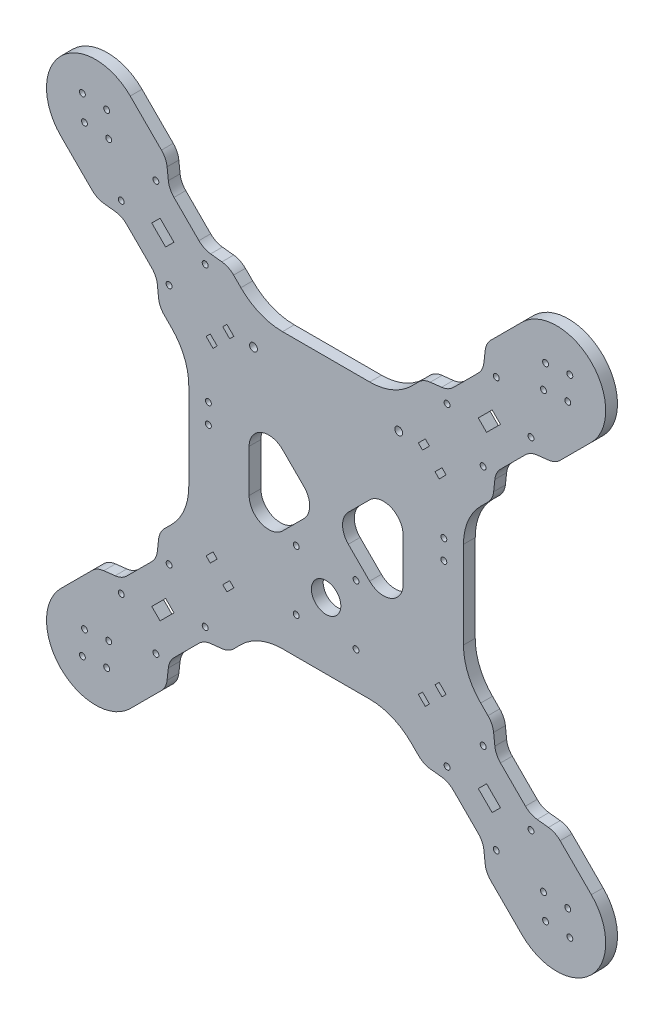
SolidWorks part; units mm, degrees
ref_plane "Front Plane" through (0, 0, 0) normal (0, 0, 1) x (1, 0, 0)
ref_plane "Top Plane" through (0, 0, 0) normal (0, 1, 0) x (1, 0, 0)
ref_plane "Right Plane" through (0, 0, 0) normal (1, 0, 0) x (0, 0, -1)
sketch "Sketch4" plane through (0, 0, 0) normal (0, 0, 1) x (1, 0, 0)
  line L0 (-117.5, 117.5) -> (117.5, -117.5) construction
  line L1 (-117.5, -117.5) -> (117.5, 117.5) construction
  line L2 (-1000, 0) -> (49000, 0) construction
  line L3 (0, -1000) -> (0, 49000) construction
  line L4 (-70, -34.6447) -> (-70, 34.6447)
  line L5 (34.6447, 70) -> (-34.6447, 70)
  line L6 (-70, 34.6447) -> (-135.1777, 99.8223)
  line L7 (-34.6447, 70) -> (-99.8223, 135.1777)
  line L8 (-135.1777, 99.8223) -> (-99.8223, 135.1777) construction
  line L9 (70, -34.6447) -> (70, 34.6447)
  line L10 (70, 34.6447) -> (135.1777, 99.8223)
  line L11 (34.6447, 70) -> (99.8223, 135.1777)
  line L12 (70, -34.6447) -> (135.1777, -99.8223)
  line L13 (34.6447, -70) -> (99.8223, -135.1777)
  line L14 (34.6447, -70) -> (-34.6447, -70)
  line L15 (-34.6447, -70) -> (-99.8223, -135.1777)
  line L16 (-70, -34.6447) -> (-135.1777, -99.8223)
  line L17 (-124.5711, 89.2157) -> (-89.2157, 124.5711) construction
  line L18 (-120.3284, 84.9731) -> (-84.9731, 120.3284) construction
  arc A0 (-135.1777, 99.8223) -> (-99.8223, 135.1777) centre (-117.5, 117.5) cw
  arc A1 (135.1777, 99.8223) -> (99.8223, 135.1777) centre (117.5, 117.5) ccw
  arc A2 (135.1777, -99.8223) -> (99.8223, -135.1777) centre (117.5, -117.5) cw
  arc A3 (-135.1777, -99.8223) -> (-99.8223, -135.1777) centre (-117.5, -117.5) ccw
  point P13 (-117.5, 117.5)
  point P17 (-135.1777, 135.1777)
  point P19 (0, 70)
  point P24 (70, 0)
  point P31 (-70, 0)
  dimension "D6" = 40
  dimension "D1" = 235
  dimension "D2" = 235
  dimension "D3" = 70
  dimension "D4" = 70
  dimension "D5" = 50
  dimension "D7" = 6
extrude "Boss-Extrude1" add sketch "Sketch4" along normal blind 6
fillet "Fillet1" radius 30 8 edges at (34.6447, -70, 3) (70, -34.6447, 3) (70, 34.6447, 3) (34.6447, 70, 3) (-34.6447, 70, 3) (-70, 34.6447, 3) (-70, -34.6447, 3) (-34.6447, -70, 3)
sketch "Sketch8" plane through (0, 0, 6) normal (0, 0, 1) x (1, 0, 0)
  line L0 (-120.3284, 84.9731) -> (-84.9731, 120.3284) construction
  line L1 (-117.5, 117.5) -> (117.5, -117.5) construction
  line L2 (-88.8622, 84.6195) -> (-84.6195, 88.8622)
  line L3 (-88.8622, 84.6195) -> (-81.7911, 77.5485)
  line L4 (-84.6195, 88.8622) -> (-77.5485, 81.7911)
  line L5 (-81.7911, 77.5485) -> (-77.5485, 81.7911)
  circle A0 centre (-104.4185, 86.7409) radius 1.5
  circle A2 centre (-80.0233, 61.6386) radius 1.5
  circle A4 centre (-86.7409, 104.4185) radius 1.5
  circle A5 centre (-61.6386, 80.0233) radius 1.5
  dimension "D1" = 3
  dimension "D2" = 10
  dimension "D3" = 12.5
  dimension "D4" = 13
  dimension "D5" = 45
  dimension "D6" = 10
  dimension "D7" = 12.5
  dimension "D8" = 45
  dimension "D9" = 13
  dimension "D10" = 6
  dimension "D11" = 3
  dimension "D12" = 22.5
  dimension "D13" = 10
sketch "Sketch9" plane through (0, 0, 6) normal (0, 0, 1) x (1, 0, 0)
  line L0 (-135.1777, 99.8223) -> (-99.8223, 135.1777) construction
  line L1 (-117.5, 117.5) -> (117.5, -117.5) construction
  circle A0 centre (-124.2175, 124.2175) radius 1.5
  circle A1 centre (-110.7825, 110.7825) radius 1.5
  circle A2 centre (-123.1569, 111.8431) radius 1.5
  circle A3 centre (-111.8431, 123.1569) radius 1.5
  dimension "D5" = 3
  dimension "D1" = 8
  dimension "D2" = 8
  dimension "D3" = 9.5
  dimension "D4" = 9.5
extrude "Cut-Extrude1" cut sketch "Sketch8" against normal through all both and the other way through all
extrude "Cut-Extrude2" cut sketch "Sketch9" against normal through all both and the other way through all
mirror "Mirror1" about plane through (0, 0, 0) normal (1, 0, 0) of "Cut-Extrude2", "Cut-Extrude1"
mirror "Mirror2" about plane through (0, 0, 0) normal (0, 1, 0) of "Mirror1"
sketch "Sketch10" plane through (0, 0, 6) normal (0, 0, 1) x (1, 0, 0)
  line L0 (-70, -34.6447) -> (-70, 34.6447) construction
  line L1 (70, -34.6447) -> (70, 34.6447) construction
  line L2 (34.6447, 70) -> (-34.6447, 70) construction
  line L3 (-49.1421, -53.3848) -> (-47.0208, -55.5061)
  line L4 (0, -201000) -> (0, 249000) construction
  line L5 (-201000, 0) -> (249000, 0) construction
  line L6 (-4.2426, 0) -> (-39.2426, 35)
  line L7 (-39.2426, 35) -> (-39.2426, -35)
  line L8 (-39.2426, -35) -> (-4.2426, 0)
  line L9 (-117.5, 117.5) -> (117.5, -117.5) construction
  line L10 (-117.5, -117.5) -> (117.5, 117.5) construction
  line L11 (0, -3.3) -> (0, 3.3) construction
  line L12 (39.2426, 35) -> (39.2426, -35)
  line L13 (4.2426, 0) -> (39.2426, 35)
  line L14 (39.2426, -35) -> (4.2426, 0)
  line L21 (3.3, 0) -> (-3.3, 0) construction
  line L22 (-57.6274, -44.8995) -> (-55.5061, -47.0208)
  line L23 (-59.0416, -50.5563) -> (-55.5061, -47.0208)
  line L24 (-61.163, -48.435) -> (-59.0416, -50.5563)
  line L25 (-61.163, 48.435) -> (-59.0416, 50.5563)
  line L26 (-61.163, 48.435) -> (-57.6274, 44.8995)
  line L27 (-57.6274, 44.8995) -> (-55.5061, 47.0208)
  line L28 (-59.0416, 50.5563) -> (-55.5061, 47.0208)
  line L29 (-61.163, -48.435) -> (-57.6274, -44.8995)
  line L30 (57.6274, 44.8995) -> (55.5061, 47.0208)
  line L31 (59.0416, 50.5563) -> (55.5061, 47.0208)
  line L32 (61.163, 48.435) -> (59.0416, 50.5563)
  line L33 (61.163, 48.435) -> (57.6274, 44.8995)
  line L34 (61.163, -48.435) -> (57.6274, -44.8995)
  line L35 (61.163, -48.435) -> (59.0416, -50.5563)
  line L36 (59.0416, -50.5563) -> (55.5061, -47.0208)
  line L37 (57.6274, -44.8995) -> (55.5061, -47.0208)
  line L38 (-52.6777, 56.9203) -> (-50.5563, 59.0416)
  line L39 (-52.6777, 56.9203) -> (-49.1421, 53.3848)
  line L40 (-49.1421, 53.3848) -> (-47.0208, 55.5061)
  line L41 (-50.5563, 59.0416) -> (-47.0208, 55.5061)
  line L42 (-50.5563, -59.0416) -> (-47.0208, -55.5061)
  line L43 (-52.6777, -56.9203) -> (-50.5563, -59.0416)
  line L44 (-52.6777, -56.9203) -> (-49.1421, -53.3848)
  line L45 (52.6777, -56.9203) -> (49.1421, -53.3848)
  line L46 (52.6777, -56.9203) -> (50.5563, -59.0416)
  line L47 (50.5563, -59.0416) -> (47.0208, -55.5061)
  line L48 (49.1421, -53.3848) -> (47.0208, -55.5061)
  line L49 (49.1421, 53.3848) -> (47.0208, 55.5061)
  line L50 (50.5563, 59.0416) -> (47.0208, 55.5061)
  line L51 (52.6777, 56.9203) -> (50.5563, 59.0416)
  line L52 (52.6777, 56.9203) -> (49.1421, 53.3848)
  line L53 (-15.25, -21) -> (15.25, -51.5) construction
  circle A0 centre (-60, 20) radius 1.5
  circle A1 centre (-60, 10) radius 1.5
  circle A2 centre (60, 20) radius 1.5
  circle A3 centre (60, 10) radius 1.5
  circle A4 centre (-15.25, -21) radius 1.5
  circle A5 centre (15.25, -21) radius 1.5
  circle A6 centre (-15.25, -51.5) radius 1.5
  circle A7 centre (15.25, -51.5) radius 1.5
  circle A8 centre (0, -36.25) radius 7.5
  circle A9 centre (-37, 55.7426) radius 2
  circle A10 centre (37, 55.7426) radius 2
  dimension "D2" = 10
  dimension "D5" = 3
  dimension "D8" = 3
  dimension "D17" = 15
  dimension "D1" = 10
  dimension "D3" = 10
  dimension "D4" = 50
  dimension "D6" = 30.5
  dimension "D7" = 30.5
  dimension "D9" = 15.25
  dimension "D10" = 21
  dimension "D11" = 3
  dimension "30" = 35
  dimension "D12" = 6
  dimension "D13" = 3
  dimension "D14" = 5
  dimension "D15" = 20
  dimension "D16" = 3
extrude "Cut-Extrude3" cut sketch "Sketch10" against normal through all both and the other way through all
fillet "Fillet2" radius 10 6 edges at (4.2426, 0, 3) (39.2426, -35, 3) (39.2426, 35, 3) (-39.2426, -35, 3) (-39.2426, 35, 3) (-4.2426, 0, 3)
sketch "Sketch11" plane through (0, 0, 6) normal (0, 0, 1) x (1, 0, 0)
  line L1 (-34.6447, 70) -> (-99.8223, 135.1777) construction
  line L2 (-80.0233, 104.065) -> (-62.3457, 86.3873)
  line L3 (-62.3457, 86.3873) -> (-49.6177, 84.9731)
  line L4 (-49.6177, 84.9731) -> (-81.4376, 116.7929)
  line L5 (-81.4376, 116.7929) -> (-80.0233, 104.065)
  line L6 (-80.0233, 104.065) -> (-74.3665, 109.7218) construction
  line L7 (-62.3457, 86.3873) -> (-56.6888, 92.0442) construction
  line L8 (-120.3284, 84.9731) -> (-84.9731, 120.3284) construction
  dimension "D1" = 45
  dimension "D2" = 8
  dimension "D3" = 10
  dimension "D4" = 10
  dimension "D5" = 5
extrude "Cut-Extrude4" cut sketch "Sketch11" against normal through all both and the other way through all
ref_plane "Plane1" through (0, 0, 0) normal (0.7071, 0.7071, 0) x (0.7071, -0.7071, 0)
mirror "Mirror4" about plane through (0, 0, 0) normal (0.7071, 0.7071, 0) of "Cut-Extrude4"
ref_axis "Axis1" through (0, 0, 0) along (0, 0, 1)
pattern_circular "CirPattern2" count 4 over 360 about axis through (0, 0, 0) along (0, 0, 1) of "Cut-Extrude4", "Mirror4"
fillet "Fillet3" radius 10 32 edges at (-49.6177, 84.9731, 3) (-62.3457, 86.3873, 3) (-80.0233, 104.065, 3) (-81.4376, 116.7929, 3) (116.7929, 81.4376, 3) (104.065, 80.0233, 3) (86.3873, 62.3457, 3) (84.9731, 49.6177, 3) (80.0233, 104.065, 3) (81.4376, 116.7929, 3) (62.3457, 86.3873, 3) (49.6177, 84.9731, 3) (116.7929, -81.4376, 3) (104.065, -80.0233, 3) (86.3873, -62.3457, 3) (84.9731, -49.6177, 3) (81.4376, -116.7929, 3) (80.0233, -104.065, 3) (62.3457, -86.3873, 3) (49.6177, -84.9731, 3) (-49.6177, -84.9731, 3) (-62.3457, -86.3873, 3) (-80.0233, -104.065, 3) (-81.4376, -116.7929, 3) (-116.7929, -81.4376, 3) (-104.065, -80.0233, 3) (-86.3873, -62.3457, 3) (-84.9731, -49.6177, 3) (-84.9731, 49.6177, 3) (-86.3873, 62.3457, 3) (-104.065, 80.0233, 3) (-116.7929, 81.4376, 3)
sketch "Sketch12" plane through (0, 0, 0) normal (0, 0, 1) x (1, 0, 0)
  line L0 (117.5, 117.5) -> (-117.5, -117.5) construction
  line L1 (-117.5, 117.5) -> (117.5, -117.5) construction
equation "\"D6@Sketch8\"=\"D2@Sketch8\""
equation "\"D7@Sketch8\"=\"D3@Sketch8\""
equation "\"D8@Sketch8\"=\"D5@Sketch8\""
equation "\"D9@Sketch8\"=\"D4@Sketch8\""
equation "\"D2@Sketch9\"=\"D1@Sketch9\""
equation "\"D4@Sketch9\"=\"D3@Sketch9\""
equation "\"D9@Sketch10\"=\"D6@Sketch10\"/2"
